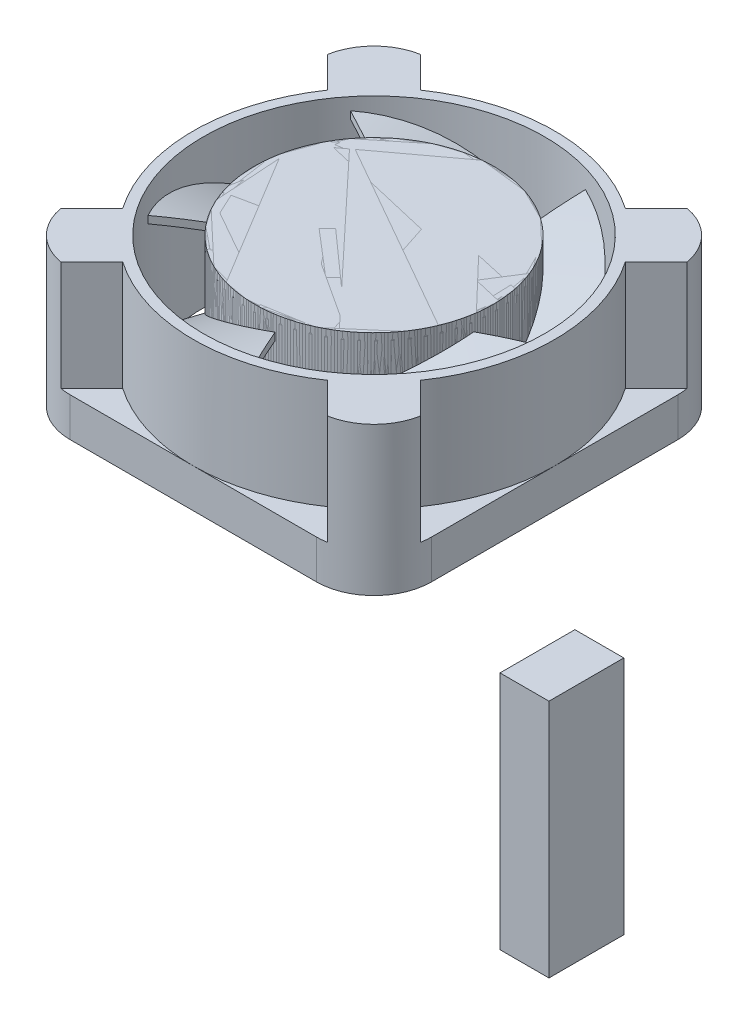
SolidWorks part; units mm, degrees
ref_plane "Ebene vorne" through (0, 0, 0) normal (0, 0, 1) x (1, 0, 0)
ref_plane "Ebene oben" through (0, 0, 0) normal (0, 1, 0) x (1, 0, 0)
ref_plane "Ebene rechts" through (0, 0, 0) normal (1, 0, 0) x (0, 0, -1)
ref_axis "Achse1" through (0, -9.5275, 0) along (0, 1, 0)
sketch "Skizze9" plane through (0, 0, 0) normal (0, 1, 0) x (1, 0, 0)
  line L0 (0, 12.55) -> (0, -12.55) construction
  line L1 (-12.55, 12.55) -> (12.55, 12.55)
  line L2 (-12.55, 12.55) -> (-12.55, -12.55)
  line L3 (-12.55, -12.55) -> (12.55, -12.55)
  line L4 (12.55, 12.55) -> (12.55, -12.55)
  line L5 (-12.55, 12.55) -> (12.55, -12.55) construction
  line L6 (-12.55, 0) -> (-12.55, 9.3327)
  line L7 (-12.55, 9.3327) -> (-10.3358, 7.1185)
  line L9 (-12.55, 0) -> (12.55, 0) construction
  line L10 (-7.1185, 10.3358) -> (-9.3327, 12.55)
  line L11 (7.1185, 10.3358) -> (9.3327, 12.55)
  line L12 (12.55, 9.3327) -> (10.3358, 7.1185)
  line L13 (-12.55, -9.3327) -> (-10.3358, -7.1185)
  line L14 (-7.1185, -10.3358) -> (-9.3327, -12.55)
  line L15 (12.55, -9.3327) -> (10.3358, -7.1185)
  line L16 (7.1185, -10.3358) -> (9.3327, -12.55)
  line L17 (-9.0564, 7.6422) -> (-6.3196, 4.9054)
  line L18 (-7.6422, 9.0564) -> (-4.9054, 6.3196)
  line L19 (7.6422, 9.0564) -> (4.9054, 6.3196)
  line L20 (9.0564, 7.6422) -> (6.3196, 4.9054)
  line L21 (-9.0564, -7.6422) -> (-6.3196, -4.9054)
  line L22 (-7.6422, -9.0564) -> (-4.9054, -6.3196)
  line L23 (7.6422, -9.0564) -> (4.9054, -6.3196)
  line L24 (9.0564, -7.6422) -> (6.3196, -4.9054)
  circle A0 centre (0, 0) radius 12.55
  circle A1 centre (0, 0) radius 11.85
  circle A2 centre (0, 0) radius 8
  dimension "D3" = 0.7
  dimension "D5" = 16
  dimension "D1" = 25.1
  dimension "D2" = 4.55
  dimension "D4" = 2
extrude "Aufsatz-Linear austragen5" add sketch "Skizze9" along normal blind 2.7 separate body contours A1 | A2 L17 A1 L21 | A2 L22 A1 L23 | A2 L24 A1 L20 | L3 L4 L1 L2 region at (-9.2966, 0, 0) region at (0, 0, -9.2966) region at (0, 0, 9.2966) region at (9.2966, 0, 0)
extrude "Aufsatz-Linear austragen6" add sketch "Skizze9<4>" along normal blind 10.3 contours A0 A1 | A0 L10 L1 L2 L7 | A0 L12 L4 L1 L11 | A0 L16 L3 L4 L15 | A0 L13 L2 L3 L14 region at (-10.3221, 0, -10.3221) region at (3.622, 0, -11.6447) region at (10.3221, 0, -10.3221) region at (-10.3221, 0, 10.3221) region at (10.3221, 0, 10.3221)
sketch "Skizze9<4>" plane through (0, 0, 0) normal (0, 1, 0) x (1, 0, 0) same geometry as "Skizze9"
fillet "Verrundung7" radius 4 4 edges at (-12.55, 5.15, -12.55) (12.55, 5.15, -12.55) (12.55, 5.15, 12.55) (-12.55, 5.15, 12.55)
sketch "Skizze10" plane through (0, 2.7, 0) normal (0, 1, 0) x (1, 0, 0)
  circle A0 centre (0, 0) radius 8.3
  dimension "D1" = 16.6
extrude "Aufsatz-Linear austragen7" add sketch "Skizze10" along normal up to surface (7.6 mm away) from offset 0.5 separate body up to face at (0, 10.3, 11.85)
ref_plane "Ebene3" through (-20, 0, 0) normal (1, 0, 0) x (0, 0, -1)
sketch "Skizze12" plane through (-20, 0, 0) normal (1, 0, 0) x (0, 0, -1)
  line L0 (8.3, 10.3) -> (-8.3, 10.3) construction
  line L1 (-6.1557, 9.8) -> (-6.25, 9.309)
  line L2 (6.25, 3.5688) -> (5.9124, 3.2)
  line L3 (-8.3, 3.2) -> (8.3, 3.2) construction
  line L4 (0, 10.3) -> (0, 16.36) construction
  line L5 (6.25, 3.5688) -> (0, 3.5688) construction
  line L6 (0, 9.309) -> (-6.25, 9.309) construction
  line L7 (7.1185, 10.3) -> (-7.1185, 10.3) construction
  arc A0 (6.25, 3.5688) -> (-6.1557, 9.8) centre (-10.9662, -15.2421) ccw
  arc A1 (-6.25, 9.309) -> (5.9124, 3.2) centre (-10.9662, -15.2421) cw
  dimension "D1" = 0.5
  dimension "D3" = 25
  dimension "D2" = 12.5
  dimension "D4" = 0.5
extrude "Aufsatz-Linear austragen8" add sketch "Skizze12" along normal up to surface (14.1748 mm away) up to face at (0, 3.2, 8.3)
sketch "Skizze13" plane through (0, 10.3, 0) normal (0, 1, 0) x (1, 0, 0)
  circle A0 centre (0, 0) radius 11.35
  circle A1 centre (0, 0) radius 11.85 construction
  dimension "D1" = 0.5
extrude "Schnitt-Linear austragen4" cut sketch "Skizze13" against normal up to surface (7.6 mm away) flip side to cut up to face at (12.1195, 2.7, 6.2765)
sketch "Skizze15" plane through (0, 10.3, 0) normal (0, 1, 0) x (1, 0, 0)
  line L0 (-9.4742, 6.25) -> (-6.7735, 4.7968)
  line L1 (-9.5357, -6.1557) -> (-7.3842, -3.7899)
  line L2 (0, 0) -> (-11.3499, 0.0563) construction
  circle A0 centre (0, 0) radius 8.3 construction
  arc A1 (-5.4615, 6.25) -> (-5.5676, -6.1557) centre (0, 0) ccw construction
  arc A2 (-9.4742, 6.25) -> (-9.5357, -6.1557) centre (0, 0) ccw construction
  arc A3 (-9.4742, 6.25) -> (-9.5357, -6.1557) centre (0, 0) ccw
  arc A4 (-6.7735, 4.7968) -> (-7.3842, -3.7899) centre (0, 0) cw
  dimension "D1" = 76
  dimension "D2" = 28
extrude "Schnitt-Linear austragen7" cut sketch "Skizze15" against normal up to surface (7.6 mm away) flip side to cut up to face at (12.1195, 2.7, 6.2765)
pattern_circular "Kreismuster2" count 5 over 360 about axis through (0, -9.5275, 0) along (0, 1, 0) of bodies 120 113
fillet "Verrundung8" radius 0.5 1 edges at (0, 10.3, 8.3)
sketch "Skizze14" plane through (0, -17.3, 0) normal (0, 1, 0) x (1, 0, 0)
  line L1 (19.75, -5.8) -> (23.15, -5.8)
  line L2 (19.75, -5.8) -> (19.75, -11)
  line L3 (19.75, -11) -> (23.15, -11)
  line L4 (23.15, -5.8) -> (23.15, -11)
extrude "Aufsatz-Linear austragen9" add sketch "Skizze14" along normal offset from surface (16.65 mm away) 20.9 separate body
